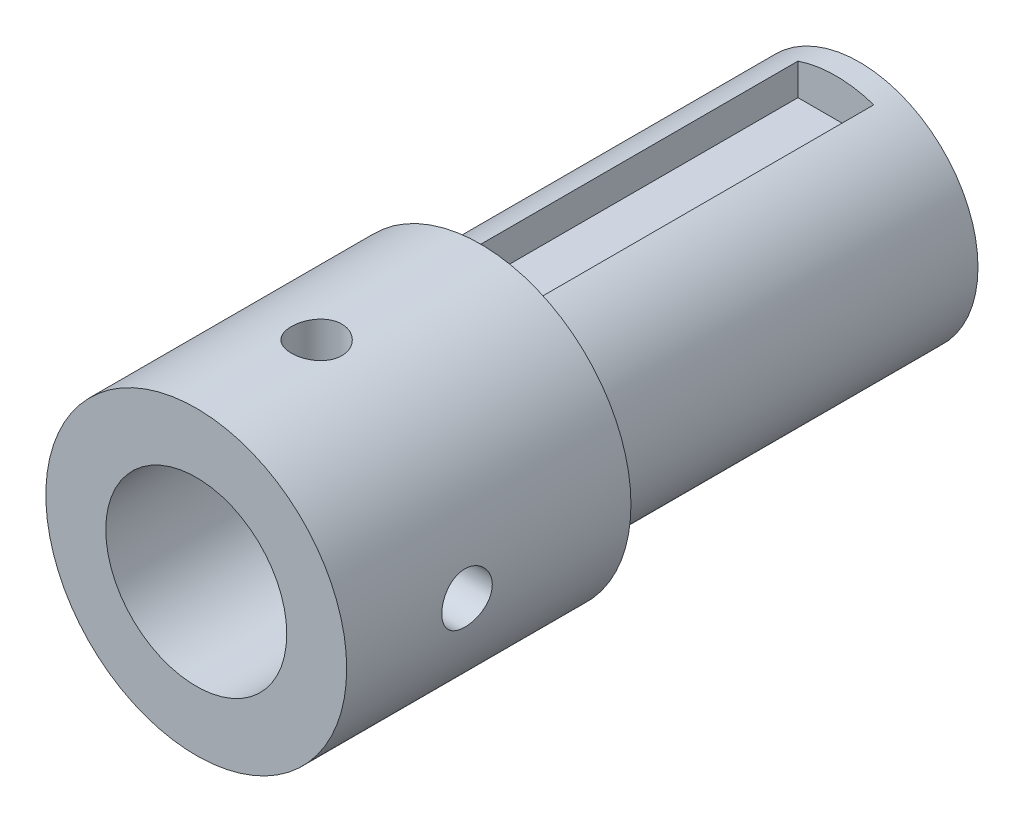
SolidWorks part; units mm, degrees
ref_plane "Front" through (0, 0, 0) normal (0, 0, 1) x (1, 0, 0)
ref_plane "Top" through (0, 0, 0) normal (0, 1, 0) x (1, 0, 0)
ref_plane "Right" through (0, 0, 0) normal (1, 0, 0) x (0, 0, -1)
sketch "Sketch1" plane through (0, 0, 0) normal (0, 0, 1) x (1, 0, 0)
  circle A0 centre (0, 0) radius 12.5
  dimension "D1" = 25
extrude "Boss-Extrude1" add sketch "Sketch1" along normal blind 40
ref_plane "Plane1" through (0, 12.5, 0) normal (0, 1, 0) x (1, 0, 0)
sketch "Sketch2" plane through (0, 12.5, 0) normal (0, 1, 0) x (1, 0, 0)
  line L0 (0, 0) -> (0, -40) construction
  line L1 (12.5, 0) -> (-12.5, 0) construction
  line L2 (-12.5, -40) -> (12.5, -40) construction
  line L4 (4, -37.5) -> (-4, -37.5)
  line L5 (4, -37.5) -> (4, -2.5)
  line L6 (4, -2.5) -> (-4, -2.5)
  line L7 (-4, -37.5) -> (-4, -2.5)
  line L8 (4, -37.5) -> (-4, -2.5) construction
  line L9 (4, -2.5) -> (-4, -37.5) construction
  point P6 (0, -20)
  dimension "D1" = 8
  dimension "D2" = 35
extrude "Cut-Extrude1" cut sketch "Sketch2" against normal blind 4
sketch "Sketch3" plane through (0, 0, 40) normal (0, 0, 1) x (1, 0, 0)
  circle A0 centre (0, 0) radius 15.875
  dimension "D1" = 31.75
extrude "Boss-Extrude2" add sketch "Sketch3" along normal blind 30
sketch "Sketch5" plane through (0, 0, 70) normal (0, 0, 1) x (1, 0, 0)
  circle A0 centre (0, 0) radius 9.5504
  dimension "D1" = 19.1008
extrude "Cut-Extrude2" cut sketch "Sketch5" against normal blind 25.4
sketch "Sketch6" plane through (0, 0, 0) normal (0, 1, 0) x (1, 0, 0)
  line L0 (0, -70) -> (0, -57.3) construction
  line L1 (-15.875, -70) -> (15.875, -70) construction
  circle A0 centre (0, -57.3) radius 2.665
  dimension "D2" = 5.33
  dimension "D1" = 12.7
extrude "Cut-Extrude3" cut sketch "Sketch6" along normal up to next
pattern_circular "CirPattern1" count 2 over 90 about axis through (0, 0, 70) along (0, 0, 1) of "Cut-Extrude3" reverse direction yes
